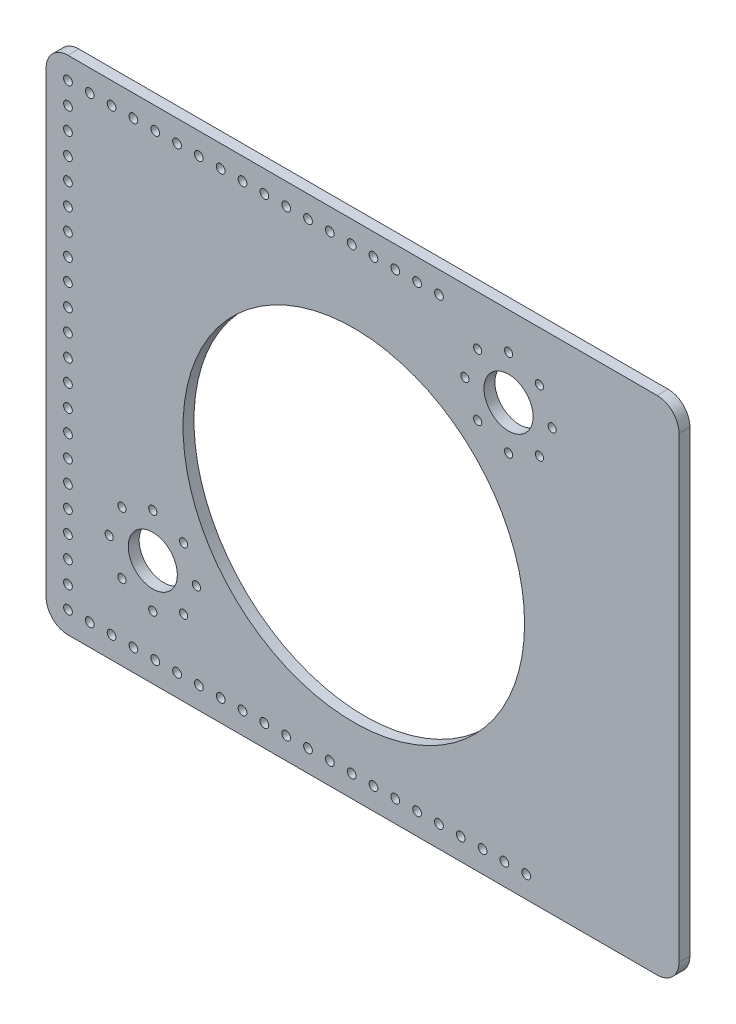
SolidWorks part; units mm, degrees
material "6061 Alloy"
ref_plane "Front Plane" through (0, 0, 0) normal (0, 0, 1) x (1, 0, 0)
ref_plane "Top Plane" through (0, 0, 0) normal (0, 1, 0) x (1, 0, 0)
ref_plane "Right Plane" through (0, 0, 0) normal (1, 0, 0) x (0, 0, -1)
sketch "Sketch1" plane through (0, 0, 0) normal (0, 0, 1) x (1, 0, 0)
  line L1 (0, 0) -> (368.3, 0)
  line L2 (0, 0) -> (0, 292.1)
  line L4 (368.3, 0) -> (368.3, 292.1)
  line L5 (0, 292.1) -> (368.3, 292.1)
  circle A0 centre (179.07, 138.43) radius 99.3775
  circle A1 centre (12.7, 279.4) radius 2.54
  circle A2 centre (25.4, 279.4) radius 2.54
  circle A3 centre (38.1, 279.4) radius 2.54
  circle A4 centre (50.8, 279.4) radius 2.54
  circle A5 centre (63.5, 279.4) radius 2.54
  circle A6 centre (76.2, 279.4) radius 2.54
  circle A7 centre (88.9, 279.4) radius 2.54
  circle A8 centre (101.6, 279.4) radius 2.54
  circle A9 centre (114.3, 279.4) radius 2.54
  circle A10 centre (127, 279.4) radius 2.54
  circle A11 centre (139.7, 279.4) radius 2.54
  circle A12 centre (152.4, 279.4) radius 2.54
  circle A13 centre (165.1, 279.4) radius 2.54
  circle A14 centre (177.8, 279.4) radius 2.54
  circle A15 centre (190.5, 279.4) radius 2.54
  circle A16 centre (203.2, 279.4) radius 2.54
  circle A17 centre (215.9, 279.4) radius 2.54
  circle A18 centre (228.6, 279.4) radius 2.54
  circle A24 centre (12.7, 266.7) radius 2.54
  circle A25 centre (12.7, 254) radius 2.54
  circle A26 centre (12.7, 241.3) radius 2.54
  circle A27 centre (12.7, 228.6) radius 2.54
  circle A28 centre (12.7, 215.9) radius 2.54
  circle A29 centre (12.7, 203.2) radius 2.54
  circle A30 centre (12.7, 190.5) radius 2.54
  circle A31 centre (12.7, 177.8) radius 2.54
  circle A32 centre (12.7, 165.1) radius 2.54
  circle A33 centre (12.7, 152.4) radius 2.54
  circle A34 centre (12.7, 139.7) radius 2.54
  circle A35 centre (12.7, 127) radius 2.54
  circle A36 centre (12.7, 114.3) radius 2.54
  circle A37 centre (12.7, 101.6) radius 2.54
  circle A38 centre (12.7, 88.9) radius 2.54
  circle A39 centre (12.7, 76.2) radius 2.54
  circle A40 centre (12.7, 63.5) radius 2.54
  circle A41 centre (12.7, 50.8) radius 2.54
  circle A42 centre (12.7, 38.1) radius 2.54
  circle A43 centre (12.7, 25.4) radius 2.54
  circle A44 centre (12.7, 12.7) radius 2.54
  circle A45 centre (25.4, 12.7) radius 2.54
  circle A46 centre (38.1, 12.7) radius 2.54
  circle A47 centre (50.8, 12.7) radius 2.54
  circle A48 centre (63.5, 12.7) radius 2.54
  circle A49 centre (76.2, 12.7) radius 2.54
  circle A50 centre (88.9, 12.7) radius 2.54
  circle A51 centre (101.6, 12.7) radius 2.54
  circle A52 centre (114.3, 12.7) radius 2.54
  circle A53 centre (127, 12.7) radius 2.54
  circle A54 centre (139.7, 12.7) radius 2.54
  circle A55 centre (152.4, 12.7) radius 2.54
  circle A56 centre (165.1, 12.7) radius 2.54
  circle A57 centre (177.8, 12.7) radius 2.54
  circle A58 centre (190.5, 12.7) radius 2.54
  circle A59 centre (203.2, 12.7) radius 2.54
  circle A60 centre (215.9, 12.7) radius 2.54
  circle A61 centre (228.6, 12.7) radius 2.54
  circle A62 centre (241.3, 12.7) radius 2.54
  circle A63 centre (254, 12.7) radius 2.54
  circle A64 centre (266.7, 12.7) radius 2.54
  circle A65 centre (279.4, 12.7) radius 2.54
  point P44 (0, 0)
  point P48 (52.9244, 279.4)
  dimension "D3" = 198.755
  dimension "D4" = 5.08
  dimension "D5" = 12.7
  dimension "D11" = 12.7
  dimension "D12" = 266.7
  dimension "D14" = 292.1
  dimension "D15" = 12.7
  dimension "D2" = 138.43
  dimension "D6" = 12.7
  dimension "D7" = 368.3
  dimension "D8" = 18
  dimension "D9" = 22
  dimension "D10" = 22
  dimension "D13" = 189.23
extrude "Boss-Extrude1" add sketch "Sketch1" along normal blind 6.35
sketch "Sketch2" plane through (0, 0, 6.35) normal (0, 0, 1) x (1, 0, 0)
  line L0 (177.2452, 140.4926) -> (-32620.0354, 37211.0747) construction
  line L1 (62.0797, 62.0797) -> (0, 62.0797) construction
  line L2 (62.0797, 62.0797) -> (62.0797, 0) construction
  line L3 (62.0797, 0) -> (0, 0) construction
  line L4 (0, 62.0797) -> (0, 0) construction
  line L5 (368.3, 292.1) -> (0, 292.1) construction
  circle A0 centre (62.0797, 62.0797) radius 14.2875
  circle A2 centre (179.07, 138.43) radius 127 construction
  circle A4 centre (62.0797, 62.0797) radius 12.7 construction
  circle A5 centre (269.1087, 245.2435) radius 14.2875
  circle A6 centre (62.0797, 62.0797) radius 25.4 construction
  circle A7 centre (62.0797, 87.4797) radius 2.3812
  circle A8 centre (80.0402, 80.0402) radius 2.3813
  circle A9 centre (87.4797, 62.0797) radius 2.3813
  circle A10 centre (80.0402, 44.1192) radius 2.3813
  circle A11 centre (62.0797, 36.6797) radius 2.3812
  circle A12 centre (44.1192, 44.1192) radius 2.3812
  circle A13 centre (36.6797, 62.0797) radius 2.3812
  circle A14 centre (44.1192, 80.0402) radius 2.3812
  circle A15 centre (269.1087, 245.2435) radius 25.4 construction
  circle A16 centre (269.1087, 270.6435) radius 2.3813
  circle A17 centre (287.0692, 263.204) radius 2.3813
  circle A18 centre (294.5087, 245.2435) radius 2.3813
  circle A19 centre (287.0692, 227.283) radius 2.3813
  circle A20 centre (269.1087, 219.8435) radius 2.3813
  circle A21 centre (251.1482, 227.283) radius 2.3813
  circle A22 centre (243.7087, 245.2435) radius 2.3813
  circle A23 centre (251.1482, 263.204) radius 2.3813
  point P36 (62.0797, 62.0797)
  point P37 (287.8974, 262.3357)
  point P38 (294.5068, 244.9345)
  point P54 (269.1087, 245.2435)
  dimension "D1" = 28.575
  dimension "D2" = 139.7
  dimension "D3" = 254
  dimension "D4" = 25.4
  dimension "D6" = 50.8
  dimension "D7" = 4.7625
  dimension "D9" = 4.7625
  dimension "D5" = 48.5
  dimension "D8" = 8
  dimension "D10" = 8
extrude "Cut-Extrude1" cut sketch "Sketch2" against normal through all
fillet "Fillet1" radius 12.7 4 edges at (0, 0, 3.175) (0, 292.1, 3.175) (368.3, 292.1, 3.175) (368.3, 0, 3.175)
